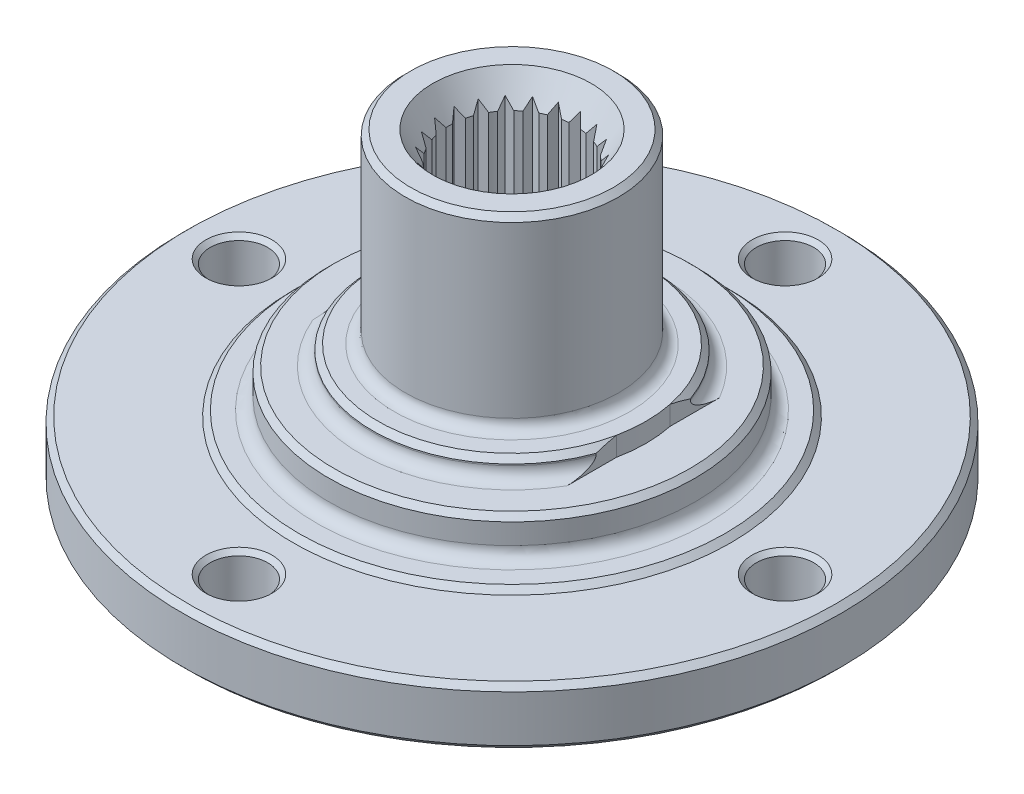
SolidWorks part; units mm, degrees
ref_plane "Plano frontal" through (0, 0, 0) normal (0, 0, 1) x (1, 0, 0)
ref_plane "Plano superior" through (0, 0, 0) normal (0, 1, 0) x (1, 0, 0)
ref_plane "Plano direito" through (0, 0, 0) normal (1, 0, 0) x (0, 0, -1)
sketch "Esboço1" plane through (0, 0, 0) normal (0, 0, 1) x (1, 0, 0)
  line L0 (0, 53.1567) -> (0, -54.6514) construction
  line L1 (11.5, 44.9115) -> (14.5, 50.1077)
  line L2 (14.5, 50.1077) -> (19.5, 50.1077)
  line L3 (19.5, 50.1077) -> (19.5, 16.1077)
  line L4 (19.5, 16.1077) -> (25.5, 16.1077)
  line L5 (25.5, 16.1077) -> (25.5, 12.6077)
  line L6 (25.5, 12.6077) -> (33.5, 12.6077)
  line L7 (33.5, 12.6077) -> (33.5, 5.6077)
  line L8 (33.5, 5.6077) -> (40, 5.6077)
  line L9 (40, 5.6077) -> (40, 4.6077)
  line L10 (40, 4.6077) -> (60.25, 4.6077)
  line L11 (60.25, 4.6077) -> (60.25, -5.8923)
  line L12 (60.25, -5.8923) -> (32.5, -5.8923)
  line L13 (32.5, -5.8923) -> (32.5, -10.8923)
  line L14 (32.5, -10.8923) -> (28.5, -10.8923)
  line L15 (28.5, -10.8923) -> (28.5, -26.3923)
  line L16 (28.5, -26.3923) -> (25.5, -26.3923)
  line L17 (25.5, -26.3923) -> (25.5, -18.7622)
  line L18 (25.5, -18.7622) -> (23.5, -18.7622)
  line L19 (23.5, -18.7622) -> (23.5, -10.781)
  line L20 (23.5, -10.781) -> (13, -10.781)
  line L21 (13, -10.781) -> (13, -10.281)
  line L22 (13, -10.281) -> (11.5, -10.281)
  line L23 (11.5, -10.281) -> (11.5, 44.9115)
  dimension "D1" = 11.5
  dimension "D2" = 14.5
  dimension "D3" = 30
  dimension "D4" = 19.5
  dimension "D5" = 34
  dimension "D6" = 37.5
  dimension "D7" = 44.5
  dimension "D8" = 45.5
  dimension "D9" = 10.5
  dimension "D10" = 20.5
  dimension "D11" = 15.5
  dimension "D12" = 0.5
  dimension "D13" = 13
  dimension "D14" = 23.5
  dimension "D15" = 25.5
  dimension "D16" = 28.5
  dimension "D17" = 32.5
  dimension "D18" = 120.5
  dimension "D19" = 80
  dimension "D20" = 67
  dimension "D21" = 51
revolve "Revolução1" add sketch "Esboço1" angle 360 about L0
chamfer "Chanfro1" distance 1 angle 45 6 edges at (-60.25, -5.8923, 0) (-60.25, 4.6077, 0) (-40, 5.6077, 0) (-33.5, 12.6077, 0) (-25.5, 16.1077, 0) (-19.5, 50.1077, 0)
fillet "Filete1" radius 2 1 edges at (-19.5, 16.1077, 0)
fillet "Filete2" radius 2.25 2 edges at (-33.5, 5.6077, 0) (-25.5, 12.6077, 0)
fillet "Filete3" radius 3.5 1 edges at (-28.5, -10.8923, 0)
fillet "Filete4" radius 3 1 edges at (-32.5, -5.8923, 0)
chamfer "Chanfro2" distance 1 angle 45 2 edges at (-25.5, -26.3923, 0) (-28.5, -26.3923, 0)
fillet "Filete5" radius 2 2 edges at (-23.5, -10.781, 0) (-25.5, -18.7622, 0)
chamfer "Chanfro3" distance 1.5 angle 45 1 edges at (-11.5, -10.281, 0)
sketch "Esboço2" plane through (0, 16.1077, 0) normal (0, 1, 0) x (1, 0, 0)
  line L0 (-25.5, 0) -> (25.5, 0) construction
  line L1 (-24, 0) -> (24, 0)
  line L2 (-25.5, 20.5977) -> (-25.5, -20.5977)
  line L3 (-25.5, 20.5977) -> (-61.793, 20.5977)
  line L4 (-61.793, 20.5977) -> (-61.793, -20.5977)
  line L5 (-61.793, -20.5977) -> (-25.5, -20.5977)
  line L6 (24, 20.5977) -> (24, -20.5977)
  line L7 (60.293, 20.5977) -> (24, 20.5977)
  line L8 (60.293, 20.5977) -> (60.293, -20.5977)
  line L9 (24, -20.5977) -> (60.293, -20.5977)
  circle A0 centre (0, 0) radius 25.5 construction
  circle A1 centre (0, 0) radius 25.5 construction
extrude "Corte-extrusão1" cut sketch "Esboço2" against normal blind 3.5
sketch "Esboço4" plane through (0, 50.1077, 0) normal (0, 1, 0) x (1, 0, 0)
  line L0 (-19.5, 0) -> (19.5, 0) construction
  line L1 (0, 19.5) -> (0, -19.5) construction
  line L2 (0, 12.5) -> (-1.3486, 11.1514)
  line L3 (0, 12.5) -> (1.3486, 11.1514)
  line L4 (-1.3486, 11.1514) -> (1.3486, 11.1514)
  line L5 (3.5217, 11.9937) -> (1.8477, 11.0796)
  line L6 (3.5217, 11.9937) -> (4.4357, 10.3197)
  line L7 (1.8477, 11.0796) -> (4.4357, 10.3197)
  line L8 (6.758, 10.5157) -> (4.8943, 10.1102)
  line L9 (6.758, 10.5157) -> (7.1634, 8.652)
  line L10 (4.8943, 10.1102) -> (7.1634, 8.652)
  line L11 (9.4469, 8.1858) -> (7.5445, 8.3218)
  line L12 (9.4469, 8.1858) -> (9.3108, 6.2833)
  line L13 (7.5445, 8.3218) -> (9.3108, 6.2833)
  line L14 (11.3704, 5.1927) -> (9.5834, 5.8592)
  line L15 (11.3704, 5.1927) -> (10.7039, 3.4057)
  line L16 (9.5834, 5.8592) -> (10.7039, 3.4057)
  line L17 (12.3728, 1.7789) -> (10.8459, 2.9219)
  line L18 (12.3728, 1.7789) -> (11.2298, 0.2521)
  line L19 (10.8459, 2.9219) -> (11.2298, 0.2521)
  line L20 (12.3728, -1.7789) -> (11.2298, -0.2521)
  line L21 (12.3728, -1.7789) -> (10.8459, -2.9219)
  line L22 (11.2298, -0.2521) -> (10.8459, -2.9219)
  line L23 (11.3704, -5.1927) -> (10.7039, -3.4057)
  line L24 (11.3704, -5.1927) -> (9.5834, -5.8592)
  line L25 (10.7039, -3.4057) -> (9.5834, -5.8592)
  line L26 (9.4469, -8.1858) -> (9.3108, -6.2833)
  line L27 (9.4469, -8.1858) -> (7.5445, -8.3218)
  line L28 (9.3108, -6.2833) -> (7.5445, -8.3218)
  line L29 (6.758, -10.5157) -> (7.1634, -8.652)
  line L30 (6.758, -10.5157) -> (4.8943, -10.1102)
  line L31 (7.1634, -8.652) -> (4.8943, -10.1102)
  line L32 (3.5217, -11.9937) -> (4.4357, -10.3197)
  line L33 (3.5217, -11.9937) -> (1.8477, -11.0796)
  line L34 (4.4357, -10.3197) -> (1.8477, -11.0796)
  line L35 (0, -12.5) -> (1.3486, -11.1514)
  line L36 (0, -12.5) -> (-1.3486, -11.1514)
  line L37 (1.3486, -11.1514) -> (-1.3486, -11.1514)
  line L38 (-3.5217, -11.9937) -> (-1.8477, -11.0796)
  line L39 (-3.5217, -11.9937) -> (-4.4357, -10.3197)
  line L40 (-1.8477, -11.0796) -> (-4.4357, -10.3197)
  line L41 (-6.758, -10.5157) -> (-4.8943, -10.1102)
  line L42 (-6.758, -10.5157) -> (-7.1634, -8.652)
  line L43 (-4.8943, -10.1102) -> (-7.1634, -8.652)
  line L44 (-9.4469, -8.1858) -> (-7.5445, -8.3218)
  line L45 (-9.4469, -8.1858) -> (-9.3108, -6.2833)
  line L46 (-7.5445, -8.3218) -> (-9.3108, -6.2833)
  line L47 (-11.3704, -5.1927) -> (-9.5834, -5.8592)
  line L48 (-11.3704, -5.1927) -> (-10.7039, -3.4057)
  line L49 (-9.5834, -5.8592) -> (-10.7039, -3.4057)
  line L50 (-12.3728, -1.7789) -> (-10.8459, -2.9219)
  line L51 (-12.3728, -1.7789) -> (-11.2298, -0.2521)
  line L52 (-10.8459, -2.9219) -> (-11.2298, -0.2521)
  line L53 (-12.3728, 1.7789) -> (-11.2298, 0.2521)
  line L54 (-12.3728, 1.7789) -> (-10.8459, 2.9219)
  line L55 (-11.2298, 0.2521) -> (-10.8459, 2.9219)
  line L56 (-11.3704, 5.1927) -> (-10.7039, 3.4057)
  line L57 (-11.3704, 5.1927) -> (-9.5834, 5.8592)
  line L58 (-10.7039, 3.4057) -> (-9.5834, 5.8592)
  line L59 (-9.4469, 8.1858) -> (-9.3108, 6.2833)
  line L60 (-9.4469, 8.1858) -> (-7.5445, 8.3218)
  line L61 (-9.3108, 6.2833) -> (-7.5445, 8.3218)
  line L62 (-6.758, 10.5157) -> (-7.1634, 8.652)
  line L63 (-6.758, 10.5157) -> (-4.8943, 10.1102)
  line L64 (-7.1634, 8.652) -> (-4.8943, 10.1102)
  line L65 (-3.5217, 11.9937) -> (-4.4357, 10.3197)
  line L66 (-3.5217, 11.9937) -> (-1.8477, 11.0796)
  line L67 (-4.4357, 10.3197) -> (-1.8477, 11.0796)
  circle A0 centre (0, 0) radius 19.5 construction
  circle A1 centre (0, 0) radius 19.5 construction
  dimension "D1" = 22
extrude "Corte-extrusão3" cut sketch "Esboço4" against normal through all
sketch "Esboço5" plane through (0, -5.8923, 0) normal (0, -1, 0) x (1, 0, 0)
  line L0 (-60.25, 0) -> (60.25, 0) construction
  circle A0 centre (0, 0) radius 60.25 construction
  circle A1 centre (0, 0) radius 50 construction
  circle A2 centre (-49.9201, 0) radius 5.25
  circle A3 centre (-35.2989, -35.2989) radius 3.25
  circle A4 centre (0, 49.9201) radius 5.25
  circle A6 centre (49.9201, 0) radius 5.25
  circle A8 centre (0, -49.9201) radius 5.25
extrude "Corte-extrusão4" cut sketch "Esboço5" against normal through all
chamfer "Chanfro4" distance 0.8 angle 45 10 edges at (55.1701, 4.6077, 0) (55.1701, -5.8923, 0) (5.25, 4.6077, -49.9201) (5.25, -5.8923, -49.9201) (-32.0489, 4.6077, -35.2989) (-32.0489, -5.8923, -35.2989) (-44.6701, 4.6077, 0) (-44.6701, -5.8923, 0) (5.25, 4.6077, 49.9201) (5.25, -5.8923, 49.9201)
